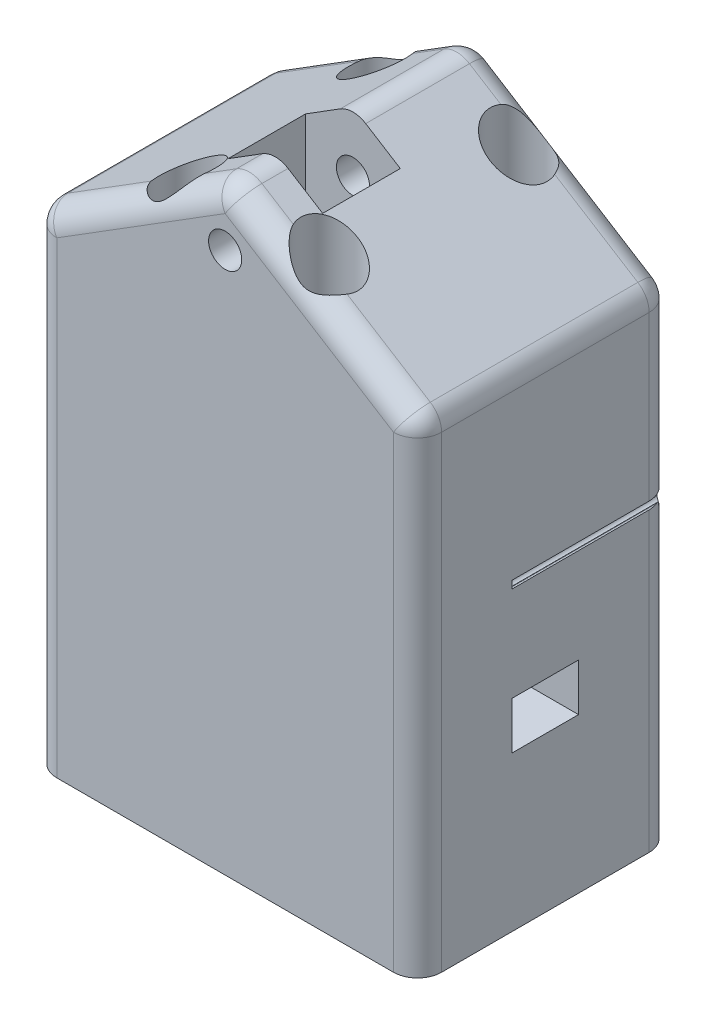
SolidWorks part; units mm, degrees
material "PLA"
ref_plane "Front Plane" through (0, 0, 0) normal (0, 0, 1) x (1, 0, 0)
ref_plane "Top Plane" through (0, 0, 0) normal (0, 1, 0) x (1, 0, 0)
ref_plane "Right Plane" through (0, 0, 0) normal (1, 0, 0) x (0, 0, -1)
sketch "Sketch1" plane through (0, 0, 0) normal (0, 1, 0) x (1, 0, 0)
  line L1 (-20.32, -13.5) -> (20.32, -13.5)
  line L2 (-20.32, -13.5) -> (-20.32, 13.5)
  line L3 (-20.32, 13.5) -> (20.32, 13.5)
  line L4 (20.32, -13.5) -> (20.32, 13.5)
  line L5 (-20.32, -13.5) -> (20.32, 13.5) construction
  line L6 (-20.32, 13.5) -> (20.32, -13.5) construction
  line L7 (-7.5, -10) -> (7.5, -10) construction
  line L8 (-7.5, -10) -> (-7.5, 10) construction
  line L9 (-7.5, 10) -> (7.5, 10) construction
  line L10 (7.5, -10) -> (7.5, 10) construction
  line L11 (-7.5, -10) -> (7.5, 10) construction
  line L12 (-7.5, 10) -> (7.5, -10) construction
  circle A0 centre (-7.5, 10) radius 1.75
  circle A1 centre (7.5, 10) radius 1.75
  circle A2 centre (7.5, -10) radius 1.75
  circle A3 centre (-7.5, -10) radius 1.75
  point P0 (0, 0)
  point P6 (0, 0)
  dimension "D3" = 3.5
  dimension "D1" = 20
  dimension "D2" = 15
  dimension "D4" = 40.64
  dimension "D5" = 27
extrude "Boss-Extrude1" add sketch "Sketch1" along normal mid plane 6.35
sketch "Sketch3" plane through (0, 3.175, 0) normal (0, 1, 0) x (1, 0, 0)
  line L1 (-20.32, -13.5) -> (20.32, -13.5)
  line L2 (-20.32, -13.5) -> (-20.32, 13.5)
  line L3 (-20.32, 13.5) -> (20.32, 13.5)
  line L4 (20.32, -13.5) -> (20.32, 13.5)
  line L5 (-20.32, -13.5) -> (20.32, 13.5) construction
  line L6 (-20.32, 13.5) -> (20.32, -13.5) construction
  circle A0 centre (-7.5, 10) radius 3
  circle A1 centre (7.5, 10) radius 3
  circle A2 centre (7.5, -10) radius 3
  circle A3 centre (-7.5, -10) radius 3
  point P0 (0, 0)
  dimension "D1" = 6
extrude "Boss-Extrude2" add sketch "Sketch3" along normal blind 44.45
sketch "Sketch4" plane through (-20.32, 0, 0) normal (-1, 0, 0) x (0, 0, 1)
  line L1 (-3.5, 13.1625) -> (3.5, 13.1625)
  line L2 (-3.5, 13.1625) -> (-3.5, 16.1625)
  line L3 (-3.5, 16.1625) -> (3.5, 16.1625)
  line L4 (3.5, 13.1625) -> (3.5, 16.1625)
  line L5 (-3.5, 13.1625) -> (3.5, 16.1625) construction
  line L6 (-3.5, 16.1625) -> (3.5, 13.1625) construction
  line L7 (-13.5, -3.175) -> (13.5, -3.175) construction
  point P0 (0, 14.6625)
  dimension "D1" = 7
  dimension "D2" = 19.3375
  dimension "D3" = 3
extrude "Cut-Extrude1" cut sketch "Sketch4" against normal through all
sketch "Sketch5" plane through (0, 0, 13.5) normal (0, 0, 1) x (1, 0, 0)
  line L0 (-20.32, 47.625) -> (20.32, 47.625)
  line L1 (20.32, 47.625) -> (0, 60.325)
  line L2 (0, 60.325) -> (-20.32, 47.625)
  dimension "D1" = 12.7
extrude "Boss-Extrude3" add sketch "Sketch5" against normal through all
sketch "Sketch6" plane through (0, 47.625, 0) normal (0, -1, 0) x (1, 0, 0)
  circle A0 centre (-7.5, 10) radius 3
  circle A1 centre (7.5, 10) radius 3
  circle A2 centre (7.5, -10) radius 3
  circle A3 centre (-7.5, -10) radius 3
  circle A4 centre (-7.5, 10) radius 3 construction
  circle A5 centre (7.5, 10) radius 3 construction
  circle A6 centre (7.5, -10) radius 3 construction
  circle A7 centre (-7.5, -10) radius 3 construction
extrude "Cut-Extrude2" cut sketch "Sketch6" against normal through all
fillet "Fillet1" radius 2.54 11 edges at (20.32, 22.225, -13.5) (-20.32, 22.225, -13.5) (-20.32, 22.225, 13.5) (20.32, 22.225, 13.5) (10.16, 53.975, -13.5) (-10.16, 53.975, -13.5) (-10.16, 53.975, 13.5) (10.16, 53.975, 13.5) (20.32, 47.625, 0) (-20.32, 47.625, 0) (0, 60.325, 0)
sketch "Sketch8" plane through (0, 0, 0) normal (0, 0, 1) x (1, 0, 0)
  line L1 (-5, 44.8697) -> (5, 44.8697)
  line L2 (-5, 44.8697) -> (-5, 59.8697)
  line L3 (-5, 59.8697) -> (5, 59.8697)
  line L4 (5, 44.8697) -> (5, 59.8697)
  line L5 (-5, 44.8697) -> (5, 59.8697) construction
  line L6 (-5, 59.8697) -> (5, 44.8697) construction
  arc A0 (1.3462, 59.4836) -> (-1.3462, 59.4836) centre (0, 57.3297) ccw construction
  point P0 (0, 52.3697)
  dimension "D1" = 10
  dimension "D2" = 15
extrude "Cut-Extrude3" cut sketch "Sketch8" along normal blind 8.2
sketch "Sketch9" plane through (0, 0, 13.5) normal (0, 0, 1) x (1, 0, 0)
  line L0 (-17.78, -3.175) -> (17.78, -3.175) construction
  circle A0 centre (0, 53.975) radius 1.75
  dimension "D1" = 3.5
  dimension "D2" = 57.15
extrude "Cut-Extrude4" cut sketch "Sketch9" against normal through all
ref_point "Point2"
sketch "Sketch10" plane through (0, 0, -13.5) normal (0, 0, -1) x (-1, 0, 0)
  line L7 (-20.32, 28.9625) -> (-18.32, 28.9625)
  line L8 (-20.32, -3.175) -> (-20.32, 46.2172) construction
  line L9 (-18.32, 28.9625) -> (-18.32, 28.1625)
  line L10 (-18.32, 28.1625) -> (-18.4726, 28.1625)
  line L11 (-20.32, 28.9625) -> (-20.32, 28.1625)
  line L12 (-20.32, 28.1625) -> (-20.1674, 28.1625)
  arc A10 (-20.1674, 28.1625) -> (-19.9179, 27.9285) centre (-20.1674, 27.9125) cw
  arc A11 (-18.4726, 28.1625) -> (-18.7221, 27.9285) centre (-18.4726, 27.9125) ccw
  arc A12 (-19.9179, 27.9285) -> (-19.8189, 27.5543) centre (-18.92, 27.9925) ccw
  arc A13 (-18.7221, 27.9285) -> (-18.8211, 27.5543) centre (-19.72, 27.9925) cw
  arc A14 (-19.8189, 27.5543) -> (-18.8211, 27.5543) centre (-19.32, 27.7975) ccw
  point P34 (-19.32, 27.2425)
  point P36 (-19.32, 28.9625)
  dimension "D11" = 0.25
  dimension "D13" = 0.555
  dimension "D15" = 1
  dimension "D9" = 2
  dimension "D10" = 0.8
  dimension "D12" = 0.4
  dimension "D14" = 1.72
  dimension "D16" = 12
extrude "Cut-Extrude5" cut sketch "Sketch10" against normal up to surface (17 mm away) up to face at (0, 14.6625, 3.5)
pattern_linear "LPattern2" count 4 spacing 2 along (-1, 0, 0) of "Cut-Extrude5"
mirror "Mirror5" about plane through (0, 0, 0) normal (1, 0, 0) of "LPattern2"
sketch "Sketch12" plane through (20.32, 0, 0) normal (1, 0, 0) x (0, 0, -1)
  line L0 (3.5, 16.1625) -> (3.5, 13.1625) construction
  line L1 (-3.5, 16.1625) -> (3.5, 16.1625)
  line L2 (-3.5, 16.1625) -> (-3.5, 18.1625)
  line L3 (-3.5, 18.1625) -> (3.5, 18.1625)
  line L4 (3.5, 16.1625) -> (3.5, 18.1625)
  dimension "D1" = 2
extrude "Cut-Extrude7" cut sketch "Sketch12" against normal through all
